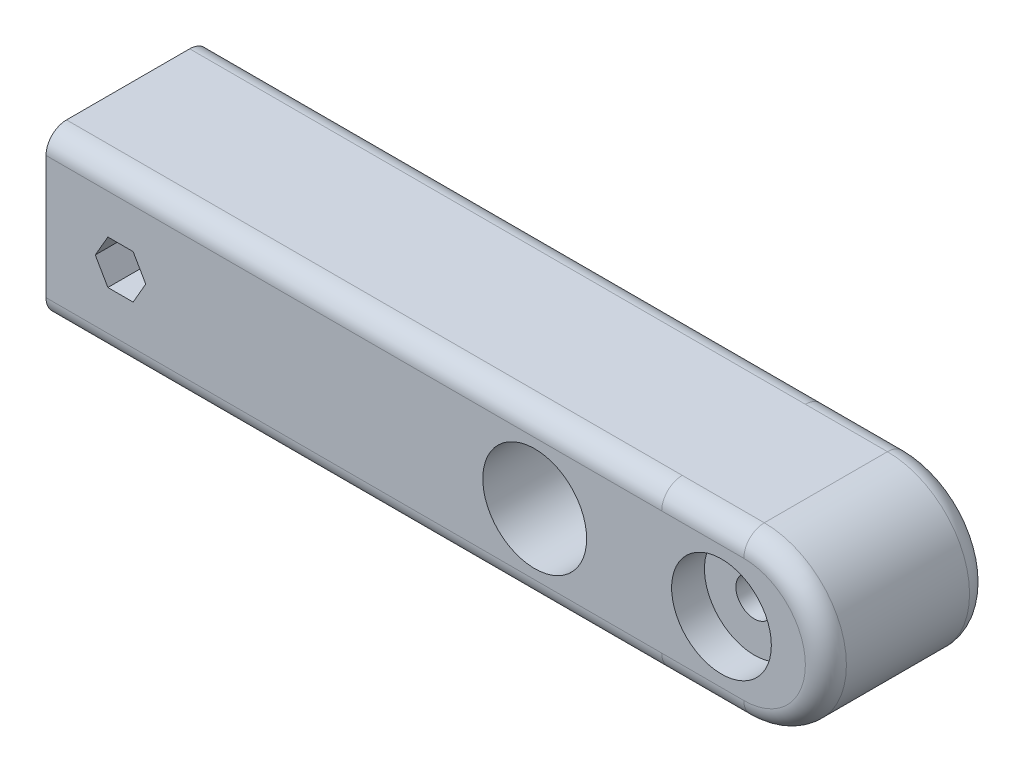
SolidWorks part; units mm, degrees
ref_plane "Alzado" through (0, 0, 0) normal (0, 0, 1) x (1, 0, 0)
ref_plane "Planta" through (0, 0, 0) normal (0, 1, 0) x (1, 0, 0)
ref_plane "Vista lateral" through (0, 0, 0) normal (1, 0, 0) x (0, 0, -1)
sketch "Croquis1" plane through (0, 0, 0) normal (0, 1, 0) x (1, 0, 0)
  line L1 (0, 0) -> (150, 0)
  line L2 (0, 0) -> (0, -40)
  line L3 (0, -40) -> (150, -40)
  line L4 (150, 0) -> (150, -40)
  dimension "D1" = 150
  dimension "D2" = 40
extrude "Saliente-Extruir1" add sketch "Croquis1" along normal blind 40
fillet "Redondeo2" radius 5 1 edges at (75, 0, 0)
fillet "Redondeo3" radius 5 3 edges at (75, 40, 0) (75, 40, 40) (75, 0, 40)
sketch "Croquis6" plane through (0, 0, 0) normal (0, 0, -1) x (-1, 0, 0)
  line L0 (0, 35) -> (0, 5) construction
  line L1 (-15.075, 14.6739) -> (-12, 20)
  line L2 (-12, 20) -> (-15.075, 25.3261)
  line L3 (-15.075, 25.3261) -> (-21.225, 25.3261)
  line L4 (-21.225, 25.3261) -> (-24.3, 20)
  line L5 (-24.3, 20) -> (-21.225, 14.6739)
  line L6 (-21.225, 14.6739) -> (-15.075, 14.6739)
  line L21 (0, 35) -> (-150, 35) construction
  circle A0 centre (-18.15, 20) radius 5.3261 construction
  dimension "D1" = 12.3
  dimension "D2" = 12
  dimension "D3" = 15
extrude "Cortar-Extruir2" cut sketch "Croquis6" against normal blind 86
sketch "Croquis7" plane through (0, 0, 40) normal (0, 0, 1) x (1, 0, 0)
  line L0 (150, 35) -> (0, 35) construction
  line L3 (150, 35) -> (150, 5) construction
  circle A0 centre (119.0584, 20) radius 12.65
  dimension "D1" = 25.3
  dimension "D2" = 15
  dimension "D3" = 30.9416
extrude "Cortar-Extruir4" cut sketch "Croquis7" against normal blind 72 contours A0
sketch "Croquis9" plane through (0, 0, 40) normal (0, 0, 1) x (1, 0, 0)
  line L0 (150, 35) -> (150, 40) construction
  line L1 (150, 40) -> (170, 40)
  line L2 (150, 40) -> (150, 0)
  line L3 (150, 0) -> (170, 0)
  arc A0 (170, 40) -> (170, 0) centre (170, 20) cw
  dimension "D1" = 20
extrude "Saliente-Extruir2" add sketch "Croquis9" against normal blind 40
fillet "Redondeo4" radius 5 6 edges at (160, 40, 0) (190, 20, 0) (160, 0, 0) (160, 40, 40) (190, 20, 40) (160, 0, 40)
sketch "Croquis10" plane through (0, 0, 40) normal (0, 0, 1) x (1, 0, 0)
  line L0 (170, 35) -> (150, 35) construction
  circle A0 centre (164.5635, 20) radius 4.5
  arc A1 (170, 5) -> (170, 35) centre (170, 20) ccw construction
  dimension "D1" = 9
  dimension "D3" = 5.4365
  dimension "D2" = 15
extrude "Cortar-Extruir5" cut sketch "Croquis10" against normal blind 60 contours A0
sketch "Croquis12" plane through (0, 0, 40) normal (0, 0, 1) x (1, 0, 0)
  circle A0 centre (164.5635, 20) radius 12.15
  dimension "D1" = 24.3
extrude "Cortar-Extruir6" cut sketch "Croquis12" against normal blind 8
sketch "Croquis13" plane through (0, 0, 0) normal (0, 0, -1) x (-1, 0, 0)
  circle A0 centre (-164.5635, 20) radius 12.15
  dimension "D1" = 24.3
extrude "Cortar-Extruir7" cut sketch "Croquis13" against normal blind 8 contours A0
sketch "Croquis14" plane through (0, 0, 0) normal (0, 0, -1) x (-1, 0, 0)
  circle A0 centre (-18.2099, 19.9408) radius 12.15
  dimension "D1" = 24.3
extrude "Cortar-Extruir8" cut sketch "Croquis14" against normal blind 8
